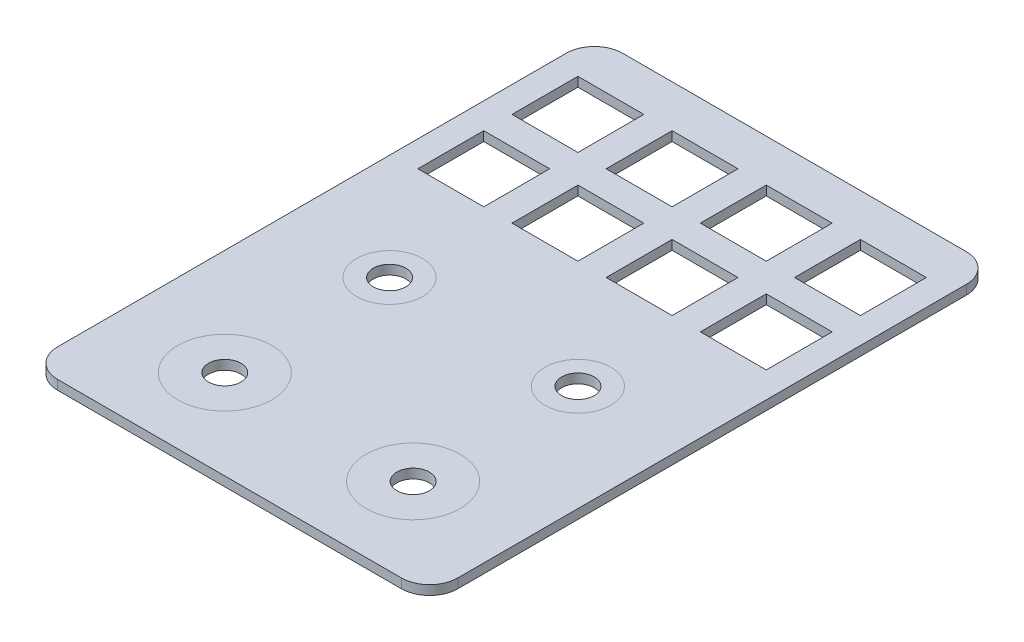
SolidWorks part; units mm, degrees
ref_plane "Plan de face" through (0, 0, 0) normal (0, 0, 1) x (1, 0, 0)
ref_plane "Plan de dessus" through (0, 0, 0) normal (0, 1, 0) x (1, 0, 0)
ref_plane "Plan de droite" through (0, 0, 0) normal (1, 0, 0) x (0, 0, -1)
sketch "Esquisse1" plane through (0, 0, 0) normal (0, 1, 0) x (1, 0, 0)
  line L1 (-42.5, -60) -> (42.5, -60)
  line L2 (-42.5, -60) -> (-42.5, 60)
  line L3 (-42.5, 60) -> (42.5, 60)
  line L4 (42.5, -60) -> (42.5, 60)
  line L5 (-42.5, -60) -> (42.5, 60) construction
  line L6 (-42.5, 60) -> (42.5, -60) construction
  point P0 (0, 0)
  dimension "D1" = 85
  dimension "D2" = 120
extrude "Boss.-Extru.1" add sketch "Esquisse1" along normal blind 2
sketch "Esquisse2" plane through (0, 2, 0) normal (0, 1, 0) x (1, 0, 0)
  line L0 (42.5, 60) -> (-42.5, 60) construction
  line L1 (-37, 51) -> (-23, 51)
  line L2 (-37, 51) -> (-37, 37)
  line L3 (-37, 37) -> (-23, 37)
  line L4 (-23, 51) -> (-23, 37)
  line L5 (-37, 51) -> (-23, 37) construction
  line L6 (-37, 37) -> (-23, 51) construction
  line L7 (-17, 51) -> (-3, 51)
  line L8 (-17, 51) -> (-17, 37)
  line L9 (-17, 37) -> (-3, 37)
  line L10 (-3, 51) -> (-3, 37)
  line L11 (-17, 51) -> (-3, 37) construction
  line L12 (-17, 37) -> (-3, 51) construction
  line L13 (3, 51) -> (17, 51)
  line L14 (3, 51) -> (3, 37)
  line L15 (3, 37) -> (17, 37)
  line L16 (17, 51) -> (17, 37)
  line L17 (3, 51) -> (17, 37) construction
  line L18 (3, 37) -> (17, 51) construction
  line L19 (23, 51) -> (37, 51)
  line L20 (23, 51) -> (23, 37)
  line L21 (23, 37) -> (37, 37)
  line L22 (37, 51) -> (37, 37)
  line L23 (23, 51) -> (37, 37) construction
  line L24 (23, 37) -> (37, 51) construction
  line L25 (23, 31) -> (37, 31)
  line L26 (23, 31) -> (23, 17)
  line L27 (23, 17) -> (37, 17)
  line L28 (37, 31) -> (37, 17)
  line L29 (23, 31) -> (37, 17) construction
  line L30 (23, 17) -> (37, 31) construction
  line L31 (17, 31) -> (3, 31)
  line L32 (17, 31) -> (17, 17)
  line L33 (17, 17) -> (3, 17)
  line L34 (3, 31) -> (3, 17)
  line L35 (17, 31) -> (3, 17) construction
  line L36 (17, 17) -> (3, 31) construction
  line L37 (-3, 31) -> (-17, 31)
  line L38 (-3, 31) -> (-3, 17)
  line L39 (-3, 17) -> (-17, 17)
  line L40 (-17, 31) -> (-17, 17)
  line L41 (-3, 31) -> (-17, 17) construction
  line L42 (-3, 17) -> (-17, 31) construction
  line L43 (-37, 31) -> (-23, 31)
  line L44 (-37, 31) -> (-37, 17)
  line L45 (-37, 17) -> (-23, 17)
  line L46 (-23, 31) -> (-23, 17)
  line L47 (-37, 31) -> (-23, 17) construction
  line L48 (-37, 17) -> (-23, 31) construction
  point P0 (-30, 44)
  point P5 (-10, 44)
  point P10 (10, 44)
  point P15 (30, 44)
  point P20 (30, 24)
  point P25 (10, 24)
  point P30 (-10, 24)
  point P35 (-30, 24)
  dimension "D1" = 14
  dimension "D2" = 14
  dimension "D3" = 20
  dimension "D4" = 20
  dimension "D5" = 20
  dimension "D6" = 10
  dimension "D7" = 16
  dimension "D8" = 20
extrude "Enlèv. mat.-Extru.1" cut sketch "Esquisse2" against normal blind 2
sketch "Esquisse3" plane through (0, 2, 0) normal (0, 1, 0) x (1, 0, 0)
  circle A0 centre (-20, -6) radius 7
  circle A1 centre (-20, -41) radius 10
  circle A2 centre (20, -6) radius 7
  circle A3 centre (20, -41) radius 10
  dimension "D1" = 14
  dimension "D6" = 20
  dimension "D2" = 35
  dimension "D3" = 20
  dimension "D4" = 20
  dimension "D5" = 6
extrude "Enlèv. mat.-Extru.2" cut sketch "Esquisse3" against normal blind 2
fillet "Congé1" radius 6 4 edges at (42.5, 1, 60) (-42.5, 1, 60) (-42.5, 1, -60) (42.5, 1, -60)
sketch "Esquisse4" plane through (0, 2, 0) normal (0, 1, 0) x (1, 0, 0)
  circle A0 centre (-20, -6) radius 7 construction
  circle A1 centre (-20, -6) radius 7
  circle A2 centre (-20, -41) radius 10 construction
  circle A3 centre (20, -41) radius 10 construction
  circle A4 centre (20, -6) radius 7 construction
  circle A5 centre (-20, -41) radius 10
  circle A6 centre (20, -41) radius 10
  circle A7 centre (20, -6) radius 7
  circle A8 centre (-20, -6) radius 3.45
  circle A9 centre (20, -6) radius 3.45
  circle A12 centre (-20, -41) radius 3.45
  circle A13 centre (20, -41) radius 3.45
  dimension "D1" = 6.9
extrude "Boss.-Extru.2" add sketch "Esquisse4" against normal blind 2 separate body
